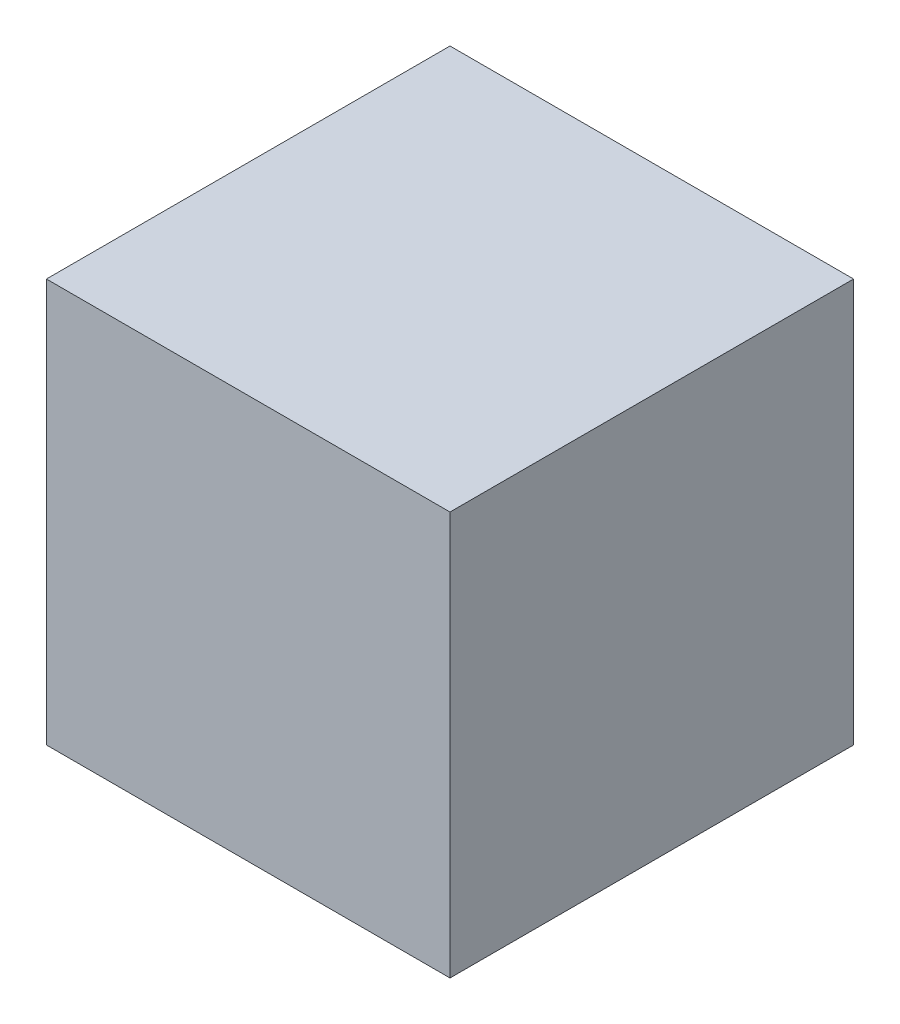
SolidWorks part; units mm, degrees
ref_plane "Front Plane" through (0, 0, 0) normal (0, 0, 1) x (1, 0, 0)
ref_plane "Top Plane" through (0, 0, 0) normal (0, 1, 0) x (1, 0, 0)
ref_plane "Right Plane" through (0, 0, 0) normal (1, 0, 0) x (0, 0, -1)
sketch "Sketch1" plane through (0, 0, 0) normal (0, 0, 1) x (1, 0, 0)
  line L1 (-20, 20) -> (20, 20)
  line L2 (-20, 20) -> (-20, -20)
  line L3 (-20, -20) -> (20, -20)
  line L4 (20, 20) -> (20, -20)
  line L5 (-20, 20) -> (20, -20) construction
  line L6 (-20, -20) -> (20, 20) construction
  point P0 (0, 0)
  dimension "D1" = 40
  dimension "D2" = 40
extrude "Boss-Extrude1" add sketch "Sketch1" along normal blind 40
sketch "Sketch2" plane through (0, 20, 0) normal (0, 0, 1) x (1, 0, 0)
  line L0 (0, -20) -> (0, 0) construction
  line L1 (20, 0) -> (-20, 0) construction
  line L2 (-20, -20) -> (20, -20) construction
  line L5 (20, -40) -> (20, 0) construction
  line L6 (-20, 0) -> (-20, -40) construction
  circle A0 centre (-14.08, -20) radius 1.59
  circle A1 centre (14.5, -20) radius 1.59
  point P7 (0, 0)
  point P15 (0, 0)
  point P17 (0, 0)
  dimension "D2" = 3.18
  dimension "D3" = 5.5
  dimension "D1" = 28.58
extrude "Cut-Extrude1" cut sketch "Sketch2" along normal blind 7 contours A0 | A1 region at (-14.08, 0, 0) region at (14.5, 0, 0)
